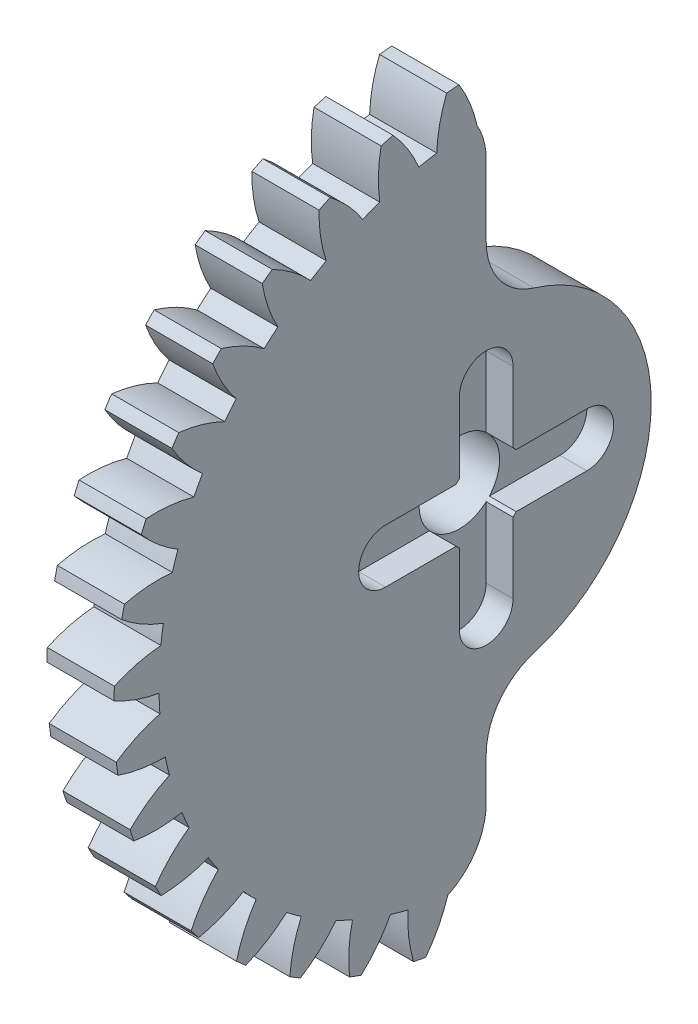
SolidWorks part; units mm, degrees
ref_plane "Plane1" through (0, 0, 0) normal (0, 0, 1) x (1, 0, 0)
ref_plane "Plane2" through (0, 0, 0) normal (0, 1, 0) x (1, 0, 0)
ref_plane "Plane3" through (0, 0, 0) normal (1, 0, 0) x (0, 0, -1)
sketch "HoldingSke" plane through (0, 0, 0) normal (0, 1, 0) x (1, 0, 0)
  line L0 (0, 0) -> (0.5461, -0.3824)
  line L1 (-15, 0) -> (100, 0) construction
  line L2 (0, 0) -> (-2.1039, 2.3779)
  line L3 (0, 0) -> (-11.863, 4.5341)
  line L4 (0, 0) -> (7.0742, 4.9534)
  line L5 (0, 0) -> (-46.8476, -17.4728)
  line L6 (0, 0) -> (-5.8027, -3.9151)
  line L7 (-2.1039, 2.3779) -> (8.6586, 51.2059)
  line L8 (-76.2, 54.61) -> (-75.2, 54.61)
  line L9 (-71.009, 38.7566) -> (-53.1078, 45.2721)
  line L10 (-76.2, 71.12) -> (104.1128, 71.12)
  line L11 (0, 0) -> (-7, 0)
  line L12 (-76.2, 101.6) -> (-76.147, 101.6)
  line L13 (24.9733, 27.94) -> (52.9518, 28.4284)
  line L14 (24.9733, 27.94) -> (24.9743, 27.94)
  line L15 (24.9733, 27.94) -> (100.4006, 29.5858)
  line L16 (-63.627, -1.5) -> (-12.827, -1.5)
  circle A0 centre (0, 0) radius 3
  circle A1 centre (0, 0) radius 24.374
  circle A2 centre (0, 0) radius 37.5
  circle A3 centre (0, 0) radius 3
  dimension "Num_teeth" = 35
  dimension "Pitch_radius" = 180.3128
  dimension "Width" = 7
  dimension "Thickness" = 7
sketch "BasProSke" plane through (0, 0, 0) normal (0, 1, 0) x (1, 0, 0)
  line L0 (-10, 0) -> (60, 0) construction
  line L1 (0, 0) -> (0, 27.75)
  line L2 (0, 0) -> (7, 0)
  line L3 (7, 0) -> (7, 27.75)
  line L4 (7, 27.75) -> (0, 27.75)
  dimension "Thickness" = 7
  dimension "Diameter" = 55.5
revolve "Base-Revolve" add sketch "BasProSke" angle 360 about L0
sketch "TooCutSke" plane through (0, 0, 0) normal (1, 0, 0) x (0, 0, -1)
  line L1 (0, 0) -> (0, 107) construction
  line L2 (0, 0) -> (-1.2704, 26.2192) construction
  line L3 (0, 0) -> (-4.702, 52.244) construction
  line L4 (-1.2704, 26.2192) -> (-2.351, 26.122) construction
  arc A0 (0.6781, 24.3646) -> (-0.6781, 24.3646) centre (0, 0) ccw
  arc A1 (2.0444, 27.7001) -> (-2.0444, 27.7001) centre (0, 0) ccw
  circle A2 centre (0, 0) radius 26.25 construction
  circle A3 centre (0, 0) radius 24.6669 construction
  arc A4 (-0.6781, 24.3646) -> (-2.0444, 27.7001) centre (-10.9336, 22.1114) ccw
  arc A5 (2.0444, 27.7001) -> (0.6781, 24.3646) centre (10.9336, 22.1114) ccw
extrude "ToothCut" cut sketch "TooCutSke" along normal through all
fillet "Breaks" [suppressed] radius 0.03 tangent propagation no
fillet "RootFillets" [suppressed] radius 0.376
pattern_circular "TeethCuts" count 35 every 10.286 about axis through (-10, 0, 0) along (1, 0, 0) of "ToothCut", "RootFillets", "Breaks"
sketch "HubNeaOneSke" plane through (0, 0, 0) normal (-1, 0, 0) x (0, 0, 1)
  circle A0 centre (0, 0) radius 24.374
  dimension "Diameter" = 48.748
extrude "HubNearOne" [suppressed] add sketch "HubNeaOneSke" along normal blind 43.0001
sketch "HubNeaBotSke" plane through (0, 0, 0) normal (-1, 0, 0) x (0, 0, 1)
  circle A0 centre (0, 0) radius 24.374
  dimension "Diameter" = 48.748
extrude "HubNearBoth" [suppressed] add sketch "HubNeaBotSke" along normal blind 21.5
ref_plane "FarPln" through (7, 0, 0) normal (1, 0, 0) x (0, 0, -1)
sketch "HubFarSke" plane through (7, 0, 0) normal (1, 0, 0) x (0, 0, -1)
  circle A0 centre (0, 0) radius 24.374
  dimension "Diameter" = 48.748
extrude "HubFar" [suppressed] add sketch "HubFarSke" along normal blind 21.5
sketch "BorSke" plane through (0, 0, 0) normal (1, 0, 0) x (0, 0, -1)
  circle A0 centre (0, 0) radius 3
  dimension "Diameter" = 6
extrude "Bore" cut sketch "BorSke" along normal mid plane 100.0001
sketch "KeySke" plane through (0, 0, 0) normal (1, 0, 0) x (0, 0, -1)
  line L0 (-1, 0) -> (-1, 4)
  line L1 (-1, 4) -> (1, 4)
  line L2 (1, 4) -> (1, 0)
  line L3 (0, 0) -> (0, 34) construction
  line L4 (-1, 0) -> (1, 0)
  dimension "Width" = 2
extrude "Keyway" [suppressed] cut sketch "KeySke" along normal mid plane 100.0001
pattern_circular "Keyway2" [suppressed] count 2 every 90 about axis through (-10, 0, 0) along (1, 0, 0) reverse direction yes
sketch "Sketch3" plane through (7, 0, 0) normal (1, 0, 0) x (0, 0, -1)
  line L0 (-1.5, -7.5) -> (-1.5, 7.5)
  line L1 (1.5, 7.5) -> (1.5, -7.5)
  arc A0 (-1.5, 7.5) -> (1.5, 7.5) centre (0, 7.5) cw
  arc A1 (1.5, -7.5) -> (-1.5, -7.5) centre (0, -7.5) cw
  circle A2 centre (0, 0) radius 3 construction
  point P6 (0, 9)
  point P7 (0, -9)
  dimension "D1" = 1.5
  dimension "D2" = 18
  dimension "D4" = 1.5
  dimension "D3" = 9
extrude "Cut-Extrude1" cut sketch "Sketch3" against normal blind 2
sketch "Sketch4" plane through (7, 0, 0) normal (1, 0, 0) x (0, 0, -1)
  line L0 (-7.5, 1.5) -> (7.5, 1.5)
  line L1 (7.5, -1.5) -> (-7.5, -1.5)
  arc A0 (7.5, 1.5) -> (7.5, -1.5) centre (7.5, 0) cw
  arc A1 (-7.5, -1.5) -> (-7.5, 1.5) centre (-7.5, 0) cw
  arc A2 (1.5, -2.5981) -> (1.5, 2.5981) centre (0, 0) ccw construction
  point P5 (-9, 0)
  point P7 (9, 0)
  dimension "D1" = 1.5
  dimension "D2" = 18
  dimension "D3" = 9
  dimension "D4" = 1.5
extrude "Cut-Extrude2" cut sketch "Sketch4" against normal blind 2
sketch "Sketch5" plane through (7, 0, 0) normal (1, 0, 0) x (0, 0, -1)
  line L0 (0, -12.2978) -> (0, -32.4838)
  line L1 (0, 33.1623) -> (0, 12.2978)
  circle A0 centre (0, 0) radius 12.2978
  arc A1 (0, -32.4838) -> (0, 33.1623) centre (0, 0.3393) ccw
extrude "Cut-Extrude3" cut sketch "Sketch5" against normal blind 10 contours L0 A1 L1 A0 region at (7, 0.3947, -15.3531)
sketch "Sketch6" plane through (7, 0, 0) normal (1, 0, 0) x (0, 0, -1)
  line L0 (-2, 2) -> (-2, 7.5)
  line L1 (2, 7.5) -> (2, 2)
  line L2 (2, 2) -> (7.5, 2)
  line L3 (7.5, -2) -> (2, -2)
  line L4 (2, -2) -> (2, -7.5)
  line L5 (-2, -7.5) -> (-2, -2)
  line L6 (-2, -2) -> (-7.5, -2)
  line L7 (-7.5, 2) -> (-2, 2)
  line L8 (1.5, -7.5) -> (1.5, -2.5981) construction
  line L9 (7.5, 1.5) -> (2.5981, 1.5) construction
  line L11 (-2.5981, 1.5) -> (-7.5, 1.5) construction
  line L12 (-1.5, 7.5) -> (-1.5, 2.5981) construction
  arc A0 (-2, 7.5) -> (2, 7.5) centre (0, 7.5) cw
  arc A1 (7.5, 2) -> (7.5, -2) centre (7.5, 0) cw
  arc A2 (2, -7.5) -> (-2, -7.5) centre (0, -7.5) cw
  arc A3 (-7.5, -2) -> (-7.5, 2) centre (-7.5, 0) cw
  arc A4 (7.5, -1.5) -> (7.5, 1.5) centre (7.5, 0) ccw construction
  arc A5 (-1.5, -7.5) -> (1.5, -7.5) centre (0, -7.5) ccw construction
  arc A6 (-7.5, 1.5) -> (-7.5, -1.5) centre (-7.5, 0) ccw construction
  arc A7 (1.5, 7.5) -> (-1.5, 7.5) centre (0, 7.5) ccw construction
  point P18 (9.5, 0)
  point P27 (0, -9.5)
  point P30 (-9.5, 0)
  point P34 (0, 0)
  point P37 (0, 9.5)
  dimension "D1" = 2
  dimension "D4" = 2
  dimension "D5" = 0.5
  dimension "D6" = 2
  dimension "D8" = 2
  dimension "D10" = 2
  dimension "D12" = 2
  dimension "D2" = 0.5
  dimension "D3" = 2
  dimension "D7" = 0.5
  dimension "D9" = 2
  dimension "D11" = 0.5
extrude "Cut-Extrude4" cut sketch "Sketch6" against normal up to vertex (2 mm away) up to point (5, 1.5, 7.5)
fillet "Fillet2" radius 5 2 edges at (3.5, 12.2978, 0) (3.5, -12.2978, 0)
ref_plane "Plane4" through (0, 24.374, 0) normal (1, 0, 0) x (0, 0, -1)
sketch "Sketch8" plane through (7, 0, 0) normal (1, 0, 0) x (0, 0, -1)
  line L0 (-2.8594, -24.2057) -> (-1.5086, -24.3273)
  line L1 (-1.5086, -24.3273) -> (1.2437, -24.575)
  line L2 (1.2437, -24.575) -> (1.2437, -32.1347)
  line L3 (1.2437, -32.1347) -> (-1.9339, -26.9792)
  line L4 (-1.9339, -26.9792) -> (-2.8594, -24.2057)
extrude "Cut-Extrude5" cut sketch "Sketch8" against normal blind 10
fillet "Fillet3" radius 5 2 edges at (3.5, 24.374, 0) (3.5, -24.463, 0)
sketch "Sketch9" plane through (0, 0, 0) normal (0, 1, 0) x (1, 0, 0)
  line L0 (-2.4485, -28.8785) -> (2, -28.8785)
  line L1 (2, -28.8785) -> (2, 12.9926)
  line L2 (2, 12.9926) -> (-3.9498, 12.9926)
  line L3 (-3.9498, 12.9926) -> (-3.9498, -28.8785)
  line L4 (-3.9498, -28.8785) -> (-2.4485, -28.8785)
  line L5 (0, 12.2978) -> (0, 3.5547) construction
  dimension "D1" = 2
extrude "Cut-Extrude6" cut sketch "Sketch9" against normal through all both and the other way through all
equation "' \"Module@HoldingSke\" = 6.35"
equation "' \"Num_teeth@HoldingSke\" = 12"
equation "' \"Ap@HoldingSke\" =  20"
equation "' \"Ap@HoldingSke\" = 20"
equation "' \"Width@HoldingSke\" = 0.5 * 25.4"
equation "' \"Hub_dia@HoldingSke\"= 1 * 25.4"
equation "' \"Hub_dia@HoldingSke\" = 1 * 25.4"
equation "' \"Overall_len@HoldingSke\" = 1.0 * 25.4"
equation "' \"Bore@HoldingSke\" = 0.75 * 25.4"
equation "' \"T_dim@HoldingSke\" = 0.1 * 25.4"
equation "' \"Width@KeySke\" = 0.25 * 25.4"
equation "' \"Show_teeth@HoldingSke\" = 13"
equation "' \"Backlash@HoldingSke\" = 0.009 * 25.4"
equation "' \"Addendum_fac@HoldingSke\" = 1.0"
equation "' \"Dedendum_fac@HoldingSke\" = 1.25"
equation "' \"Dedendum_add@HoldingSke\" = 0.00005 * 25.4"
equation "' \"Clearance_fac@HoldingSke\" = 0.25"
equation "\"Pitch@HoldingSke\" = 1 / \"Module@HoldingSke\""
equation "\"Overcut_dia@TooCutSke\" = (\"Num_teeth@HoldingSke\" + 2 * \"Addendum_fac@HoldingSke\") / \"Pitch@HoldingSke\" + 0.002 * 25.4"
equation "\"Pitch_dia@TooCutSke\" = \"Num_teeth@HoldingSke\" / \"Pitch@HoldingSke\""
equation "\"Base_dia@TooCutSke\" = \"Num_teeth@HoldingSke\" / \"Pitch@HoldingSke\" * cos((\"Ap@HoldingSke\"  * 3.14159265 / 180))"
equation "\"Root_dia@TooCutSke\" = (\"Num_teeth@HoldingSke\" + 2) / \"Pitch@HoldingSke\" - 2 * (\"Addendum_fac@HoldingSke\" + \"Dedendum_fac@HoldingSke\") / \"Pitch@HoldingSke\" - \"Dedendum_add@HoldingSke\" * 2"
equation "\"Half_ang@TooCutSke\" = 180 / \"Num_teeth@HoldingSke\""
equation "\"Half_CT@TooCutSke\" = \"Num_teeth@HoldingSke\" / \"Pitch@HoldingSke\" * sin((3.14159265 / 2 / \"Num_teeth@HoldingSke\")) / 2 - 7 * \"Backlash@HoldingSke\" / 4"
equation "\"Flank_rad@TooCutSke\" = \"Num_teeth@HoldingSke\" / \"Pitch@HoldingSke\" / 5"
equation "\"Radius@RootFillets\" = \"Clearance_fac@HoldingSke\" / \"Pitch@HoldingSke\" + \"Dedendum_add@HoldingSke\""
equation "\"Break_rad@Breaks\" = 0.02 / \"Pitch@HoldingSke\""
equation "\"Thickness@HoldingSke\" = \"Width@HoldingSke\""
equation "\"OAL@HoldingSke\" = \"Thickness@HoldingSke\""
equation "\"MHD@HoldingSke\" = (\"Num_teeth@HoldingSke\" + 2) / \"Pitch@HoldingSke\" - 2 * (\"Addendum_fac@HoldingSke\" + \"Dedendum_fac@HoldingSke\")  / \"Pitch@HoldingSke\" - \"Dedendum_add@HoldingSke\" * 2"
equation "\"MBD@HoldingSke\" = (\"Num_teeth@HoldingSke\" + 2) / \"Pitch@HoldingSke\" - 2 * (\"Addendum_fac@HoldingSke\" + \"Dedendum_fac@HoldingSke\")  / \"Pitch@HoldingSke\" - \"Dedendum_add@HoldingSke\" * 2 - 0.002 * 25.4"
equation "\"MHD@HoldingSke\" = ((sgn( \"MHD@HoldingSke\" - \"Hub_dia@HoldingSke\" )-1)*( \"MHD@HoldingSke\" - \"Hub_dia@HoldingSke\" ))/-2+ \"Hub_dia@HoldingSke\""
equation "\"MBD@HoldingSke\" = ((sgn( \"MBD@HoldingSke\" - \"Bore@HoldingSke\" )-1)*( \"MBD@HoldingSke\" - \"Bore@HoldingSke\" ))/-2+ \"Bore@HoldingSke\""
equation "\"OAL@HoldingSke\" = ((sgn( \"OAL@HoldingSke\" - \"Overall_len@HoldingSke\" )+1)*( \"OAL@HoldingSke\" - \"Overall_len@HoldingSke\" ))/2 + \"Overall_len@HoldingSke\" + 0.000002 * 25.4"
equation "\"Num_teeth@TeethCuts\" = int( \"Show_teeth@HoldingSke\" ) + 1"
equation "\"Num_teeth@TeethCuts\" = ((sgn( \"Num_teeth@TeethCuts\" - \"Num_teeth@HoldingSke\" )-1)*( \"Num_teeth@TeethCuts\" - \"Num_teeth@HoldingSke\" ))/-2+ \"Num_teeth@HoldingSke\""
equation "\"Num_teeth@TeethCuts\" = ((sgn( \"Num_teeth@TeethCuts\" - 2.0)+1)*( \"Num_teeth@TeethCuts\" - 2.0))/2 +2.0"
equation "\"Angle@TeethCuts\" = 360.0 / \"Num_teeth@HoldingSke\""
equation "\"Diameter@BasProSke\" = (\"Num_teeth@HoldingSke\" + 2 * \"Addendum_fac@HoldingSke\") / \"Pitch@HoldingSke\""
equation "\"Thickness@BasProSke\"  = \"Thickness@HoldingSke\""
equation "' \"Fillet_rad@BasProSke\" =  \"Thickness@HoldingSke\" * 0.05"
equation "' \"Fillet_rad@BasProSke\" = \"Thickness@HoldingSke\" * 0.05"
equation "\"MHD@HoldingSke\" = ((sgn( \"MHD@HoldingSke\" - \"Root_dia@TooCutSke\" )-1)*( \"MHD@HoldingSke\" - \"Root_dia@TooCutSke\" ))/-2+ \"Root_dia@TooCutSke\""
equation "\"Diameter@HubNeaOneSke\" = \"MHD@HoldingSke\""
equation "\"Length@HubNearOne\" = \"OAL@HoldingSke\" - \"Thickness@BasProSke\""
equation "\"Diameter@HubNeaBotSke\" = \"MHD@HoldingSke\""
equation "\"Length@HubNearBoth\" = ( \"OAL@HoldingSke\" - \"Thickness@BasProSke\" ) / 2.0"
equation "\"Thickness@FarPln\" = \"Thickness@BasProSke\""
equation "\"Diameter@HubFarSke\" = \"MHD@HoldingSke\""
equation "\"Length@HubFar\" = ( \"OAL@HoldingSke\" - \"Thickness@BasProSke\" ) / 2.0"
equation "\"Diameter@BorSke\" = \"MBD@HoldingSke\""
equation "\"D1@Bore\" = \"OAL@HoldingSke\" * 2.0"
equation "\"D1@Keyway\" = \"OAL@HoldingSke\" * 2.0"
equation "\"Offset@KeySke\" = \"T_dim@HoldingSke\" + \"MBD@HoldingSke\" / 2.0"
